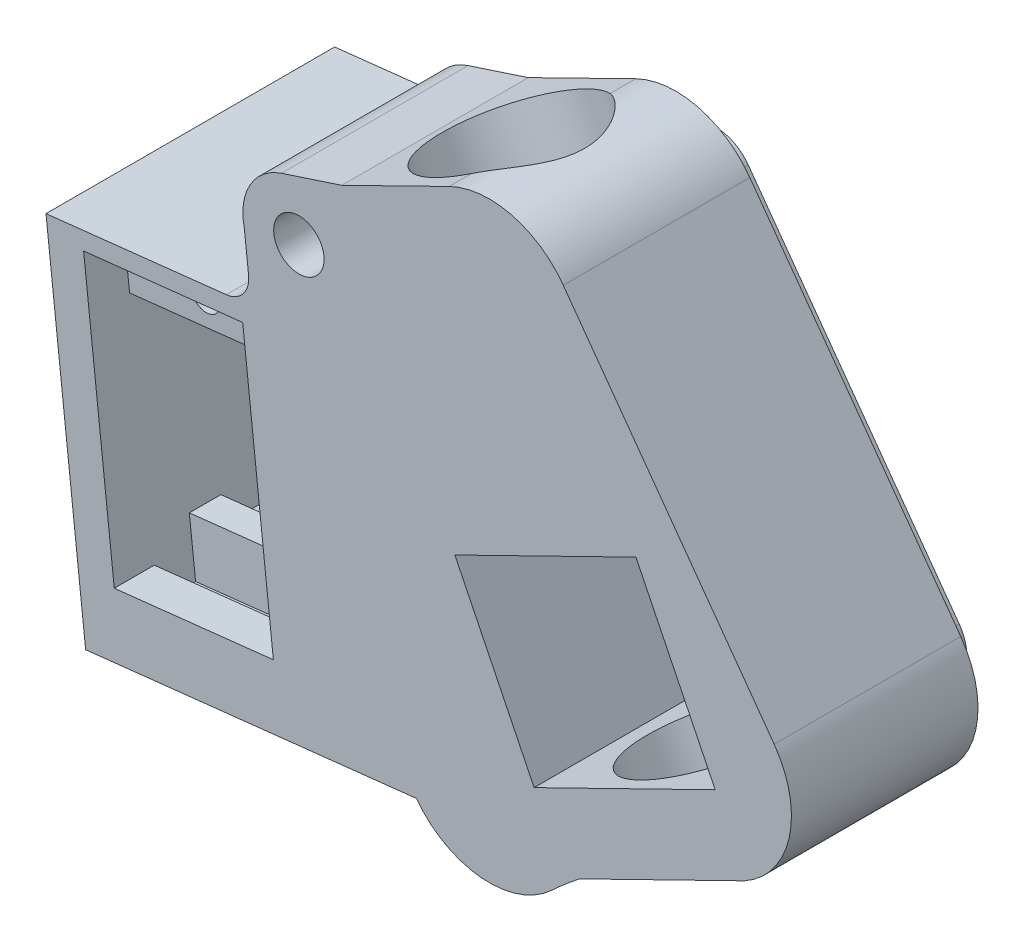
SolidWorks part; units mm, degrees
note: The reader was unsure of these and kept them because the rebuilt part matched: shared geometry of "Sketch1<4>".
ref_plane "Front Plane" through (0, 0, 0) normal (0, 0, 1) x (1, 0, 0)
ref_plane "Top Plane" through (0, 0, 0) normal (0, 1, 0) x (1, 0, 0)
ref_plane "Right Plane" through (0, 0, 0) normal (1, 0, 0) x (0, 0, -1)
sketch "Sketch1" plane through (0, 0, 0) normal (0, 0, 1) x (1, 0, 0)
  line L0 (767.9848, 261.423) -> (751.2472, 284.5967) construction
  line L1 (745.4984, 250.2176) -> (745.4984, 282.7377) construction
  line L2 (767.9848, 261.423) -> (751.2472, 284.5967)
  line L3 (745.4984, 250.2176) -> (745.4984, 282.7377)
  line L5 (771.2793, 263.8025) -> (754.5418, 286.9763)
  line L6 (732.1798, 275.0395) -> (736.9594, 273.4778) construction
  line L7 (736.9594, 285.0516) -> (732.1797, 283.4899) construction
  line L8 (732.1798, 275.0395) -> (736.9594, 273.4778)
  line L9 (736.9594, 285.0516) -> (732.1797, 283.4899)
  line L10 (736.9594, 285.0516) -> (745.4834, 289.236)
  line L11 (739.1483, 270.4598) -> (741.4784, 249.4207)
  line L12 (756.5148, 247.1568) -> (767.2365, 252.4067) construction
  line L13 (741.4344, 250.2176) -> (741.4344, 282.7377) construction
  line L14 (755.8389, 246.8259) -> (768.8985, 253.2205)
  arc A0 (745.4984, 250.2176) -> (750.8405, 247.8971) centre (748.6734, 250.2176) ccw construction
  arc A1 (766.2496, 256.5018) -> (750.8405, 247.8971) centre (775.9784, 220.98) ccw construction
  arc A2 (766.2496, 256.5018) -> (767.9848, 261.423) centre (765.4109, 259.564) ccw construction
  arc A3 (751.2472, 284.5967) -> (745.4984, 282.7377) centre (748.6734, 282.7377) ccw construction
  arc A4 (745.4984, 250.2176) -> (750.8405, 247.8971) centre (748.6734, 250.2176) ccw
  arc A5 (766.2496, 256.5018) -> (750.8405, 247.8971) centre (775.9784, 220.98) ccw
  arc A6 (766.2496, 256.5018) -> (767.9848, 261.423) centre (765.4109, 259.564) ccw
  arc A7 (751.2472, 284.5967) -> (745.4984, 282.7377) centre (748.6734, 282.7377) ccw
  arc A8 (754.5418, 286.9763) -> (745.4834, 289.236) centre (748.6734, 282.7377) ccw
  arc A9 (741.4784, 249.4207) -> (753.6143, 244.927) centre (748.6734, 250.2176) ccw
  arc A10 (755.8389, 246.8259) -> (753.6143, 244.927) centre (775.9784, 220.98) ccw
  arc A11 (768.2831, 252.9192) -> (771.2793, 263.8025) centre (765.4109, 259.564) ccw
  arc A12 (739.1483, 270.4598) -> (736.9594, 273.4778) centre (735.9733, 270.4598) ccw construction
  arc A14 (732.1797, 283.4899) -> (732.1798, 275.0395) centre (733.5603, 279.2647) ccw construction
  arc A15 (739.1483, 270.4598) -> (736.9594, 273.4778) centre (735.9733, 270.4598) ccw
  arc A17 (732.1797, 283.4899) -> (732.1798, 275.0395) centre (733.5603, 279.2647) ccw
  arc A18 (754.5418, 286.9763) -> (741.4344, 282.7377) centre (748.6734, 282.7377) ccw construction
  arc A19 (741.4344, 250.2176) -> (753.6143, 244.927) centre (748.6734, 250.2176) ccw construction
  arc A20 (767.3231, 252.5821) -> (753.6143, 244.927) centre (775.9784, 220.98) ccw construction
  arc A21 (767.3231, 252.5821) -> (771.2793, 263.8025) centre (765.4109, 259.564) ccw construction
  dimension "D1" = 4.064
extrude "Boss-Extrude1" add sketch "Sketch1" along normal blind 15.06 contours L9 A17 L8 A15 L11 A9 A10 A11 L5 A8 L10 A7 L2 A6 A5 A4 L3 | L2 A7 L3 A4 A5 A6
sketch "Sketch4" plane through (0, 0, 15.06) normal (0, 0, 1) x (1, 0, 0)
  line L0 (756.5148, 247.1568) -> (767.2365, 252.4067) construction
  line L1 (746.963, 293.8107) -> (736.2413, 288.5608) construction
  line L2 (756.5148, 247.1568) -> (767.2365, 252.4067)
  line L3 (746.963, 293.8107) -> (736.2413, 288.5608)
  line L4 (746.963, 293.8107) -> (767.2365, 252.4067)
  line L5 (756.5148, 247.1568) -> (736.2413, 288.5608)
extrude "Boss-Extrude2" add sketch "Sketch1<4>" against normal blind 3.175 contours L2 A7 L3 A4 A5 A6
sketch "Sketch1<4>" plane through (0, 0, 0) normal (0, 0, 1) x (1, 0, 0) same geometry as "Sketch1"
sketch "Sketch7" plane through (759.7828, 84.1474, 0) normal (-0.9939, -0.1101, 0) x (0, 0, 1)
  line L0 (15.06, 187.4516) -> (15.06, 166.2838) construction
  line L1 (0, 191.1833) -> (15.06, 191.1833)
  line L2 (0, 191.1833) -> (0, 162.6083)
  line L3 (0, 162.6083) -> (15.06, 162.6083)
  line L4 (15.06, 191.1833) -> (15.06, 162.6083)
  line L6 (0, 187.4516) -> (0, 166.2838) construction
  dimension "D1" = 28.575
extrude "Boss-Extrude3" add sketch "Sketch7" along normal blind 25.4 and the other way blind 2.54
sketch "Sketch8" plane through (0, 0, 15.06) normal (0, 0, 1) x (1, 0, 0)
  line L2 (716.6374, 242.9715) -> (742.8795, 245.8778) construction
  line L3 (723.9356, 257.8352) -> (725.4734, 243.9501) construction
  line L4 (716.6374, 242.9715) -> (713.4919, 271.3728) construction
  line L5 (723.9356, 257.8352) -> (724.616, 251.6912) construction
  circle A0 centre (723.9356, 257.8352) radius 5.1
  dimension "D1" = 10.2
  dimension "D2" = 13.97
  dimension "D3" = 8.89
sketch "Sketch9" plane through (0, 0, 15.06) normal (0, 0, 1) x (1, 0, 0)
  line L1 (716.6374, 242.9715) -> (742.8795, 245.8778) construction
  line L2 (716.6374, 242.9715) -> (713.4919, 271.3728) construction
  line L8 (731.5337, 249.7323) -> (729.1012, 271.696)
  line L9 (729.1012, 271.696) -> (716.4784, 270.298)
  line L10 (716.4784, 270.298) -> (718.9109, 248.3343)
  line L11 (718.9109, 248.3343) -> (731.5337, 249.7323)
  dimension "D1" = 22.098
  dimension "D2" = 5.08
  dimension "D3" = 2.85
  dimension "D4" = 12.7
extrude "Cut-Extrude1" cut sketch "Sketch9" against normal offset from surface (14.552 mm away) 0.254 from offset 0.254 up to face at (743.0241, 266.2605, 0) offset against normal yes
sketch "Sketch11" plane through (0, 0, 0) normal (0, 0, -1) x (-1, 0, 0)
  line L0 (-713.4919, 271.3728) -> (-732.3764, 273.4643)
  line L1 (-713.4919, 271.3728) -> (-735.8301, 273.8468) construction
  line L2 (-732.3764, 273.4643) -> (-735.5219, 245.063)
  line L3 (-716.6374, 242.9715) -> (-742.8795, 245.8778) construction
  line L4 (-735.5219, 245.063) -> (-722.9488, 243.6705)
  line L5 (-739.1484, 220.9799) -> (-739.1483, 270.4598) construction
  line L6 (-739.1484, 220.9799) -> (-739.1483, 270.4598) construction
  line L7 (-735.5219, 245.063) -> (-739.1484, 245.4646)
  line L8 (-739.1484, 245.4646) -> (-739.1483, 270.4598)
  line L10 (-736.9594, 273.4778) -> (-735.8301, 273.8468)
  line L16 (-732.1797, 283.4899) -> (-736.9594, 285.0516)
  line L17 (-736.9594, 285.0516) -> (-745.4834, 289.236)
  line L18 (-754.5418, 286.9763) -> (-771.2793, 263.8025)
  line L19 (-768.8985, 253.2205) -> (-755.8389, 246.8259)
  line L21 (-742.8795, 245.8778) -> (-716.6374, 242.9715)
  line L22 (-716.6374, 242.9715) -> (-713.4919, 271.3728)
  line L23 (-713.4919, 271.3728) -> (-735.8301, 273.8468)
  line L25 (-735.8301, 273.8468) -> (-732.1798, 275.0395)
  line L26 (-732.1797, 283.4899) -> (-736.9594, 285.0516)
  line L27 (-736.9594, 285.0516) -> (-745.4834, 289.236)
  line L28 (-754.5418, 286.9763) -> (-771.2793, 263.8025)
  line L29 (-768.8985, 253.2205) -> (-755.8389, 246.8259)
  line L31 (-742.8795, 245.8778) -> (-722.9488, 243.6705)
  line L33 (-713.4919, 271.3728) -> (-735.8301, 273.8468)
  line L35 (-735.8301, 273.8468) -> (-732.1798, 275.0395)
  arc A0 (-736.9594, 273.4778) -> (-739.1483, 270.4598) centre (-735.9733, 270.4598) ccw construction
  arc A1 (-736.9594, 273.4778) -> (-739.1483, 270.4598) centre (-735.9733, 270.4598) ccw
  arc A6 (-745.4834, 289.236) -> (-754.5418, 286.9763) centre (-748.6734, 282.7377) ccw
  arc A7 (-771.2793, 263.8025) -> (-768.8985, 253.2205) centre (-765.4109, 259.564) ccw
  arc A8 (-753.6143, 244.927) -> (-755.8389, 246.8259) centre (-775.9784, 220.98) ccw
  arc A9 (-753.6143, 244.927) -> (-742.8795, 245.8778) centre (-748.6734, 250.2176) ccw
  arc A11 (-732.1798, 275.0395) -> (-732.1797, 283.4899) centre (-733.5603, 279.2647) ccw
  arc A12 (-745.4834, 289.236) -> (-754.5418, 286.9763) centre (-748.6734, 282.7377) ccw
  arc A13 (-771.2793, 263.8025) -> (-768.8985, 253.2205) centre (-765.4109, 259.564) ccw
  arc A14 (-753.6143, 244.927) -> (-755.8389, 246.8259) centre (-775.9784, 220.98) ccw
  arc A15 (-753.6143, 244.927) -> (-742.8795, 245.8778) centre (-748.6734, 250.2176) ccw
  arc A17 (-732.1798, 275.0395) -> (-732.1797, 283.4899) centre (-733.5603, 279.2647) ccw
  dimension "D1" = 19
  dimension "D2" = 0
extrude "Boss-Extrude4" add sketch "Sketch11" along normal blind 8.1
extrude "Cut-Extrude3" cut sketch "Sketch8" against normal through all
sketch "Sketch15" plane through (48.6865, -99.4313, 0) normal (0.4398, -0.8981, 0) x (0.8981, 0.4398, 0)
  line L0 (787.3745, 15.06) -> (801.9156, 15.06) construction
  line L1 (801.9156, 15.06) -> (801.9156, 0) construction
  circle A0 centre (794.096, 7.5321) radius 5.969 construction
  circle A1 centre (794.096, 7.5321) radius 6.096
  dimension "D1" = 11.938
  dimension "D2" = 7.5279
  dimension "D3" = 7.8196
  dimension "D4" = 0.127
extrude "Cut-Extrude4" cut sketch "Sketch15" against normal through all
sketch "Sketch20" plane through (0, 0, 15.06) normal (0, 0, 1) x (1, 0, 0)
  line L0 (718.9109, 248.3343) -> (731.5337, 249.7323) construction
  line L1 (716.4784, 270.298) -> (718.9109, 248.3343) construction
  line L2 (729.1012, 271.696) -> (716.4784, 270.298) construction
  line L3 (731.5337, 249.7323) -> (729.1012, 271.696) construction
  line L4 (718.9109, 248.3343) -> (731.5337, 249.7323)
  line L5 (732.1798, 275.0395) -> (735.8301, 273.8468)
  line L6 (735.8301, 273.8468) -> (713.4919, 271.3728)
  line L7 (713.4919, 271.3728) -> (716.6374, 242.9715)
  line L8 (716.6374, 242.9715) -> (742.8795, 245.8778)
  line L9 (755.8389, 246.8259) -> (768.8985, 253.2205)
  line L10 (732.1798, 275.0395) -> (735.8301, 273.8468)
  line L11 (735.8301, 273.8468) -> (713.4919, 271.3728)
  line L12 (713.4919, 271.3728) -> (716.6374, 242.9715)
  line L13 (716.6374, 242.9715) -> (742.8795, 245.8778)
  line L15 (716.4784, 270.298) -> (718.9109, 248.3343)
  line L16 (729.1012, 271.696) -> (716.4784, 270.298)
  line L17 (731.5337, 249.7323) -> (729.1012, 271.696)
  line L26 (755.8389, 246.8259) -> (768.8985, 253.2205)
  line L27 (771.2793, 263.8025) -> (754.5418, 286.9763)
  line L29 (745.4834, 289.236) -> (736.9594, 285.0516)
  line L30 (745.4834, 289.236) -> (736.9594, 285.0516)
  line L31 (736.9594, 285.0516) -> (732.1797, 283.4899)
  line L32 (736.9594, 285.0516) -> (732.1797, 283.4899)
  line L36 (771.2793, 263.8025) -> (754.5418, 286.9763)
  arc A2 (742.8795, 245.8778) -> (753.6143, 244.927) centre (748.6734, 250.2176) ccw
  arc A3 (755.8389, 246.8259) -> (753.6143, 244.927) centre (775.9784, 220.98) ccw
  arc A4 (742.8795, 245.8778) -> (753.6143, 244.927) centre (748.6734, 250.2176) ccw
  arc A9 (755.8389, 246.8259) -> (753.6143, 244.927) centre (775.9784, 220.98) ccw
  arc A10 (768.8985, 253.2205) -> (771.2793, 263.8025) centre (765.4109, 259.564) ccw
  arc A14 (732.1797, 283.4899) -> (732.1798, 275.0395) centre (733.5603, 279.2647) ccw
  arc A15 (732.1797, 283.4899) -> (732.1798, 275.0395) centre (733.5603, 279.2647) ccw
  arc A16 (768.8985, 253.2205) -> (771.2793, 263.8025) centre (765.4109, 259.564) ccw
  arc A18 (754.5418, 286.9763) -> (745.4834, 289.236) centre (748.6734, 282.7377) ccw
  arc A19 (754.5418, 286.9763) -> (745.4834, 289.236) centre (748.6734, 282.7377) ccw
  dimension "D1" = 0
extrude "Cut-Extrude6" cut sketch "Sketch20" against normal up to surface (0.254 mm away) up to face at (729.0356, 257.8352, 14.806)
sketch "Sketch22" plane through (-18.4589, 166.6692, 0) normal (-0.1101, 0.9939, 0) x (0.9939, 0.1101, 0)
  line L0 (741.8783, -0.254) -> (741.8783, -14.806) construction
  line L1 (741.8783, -8.631) -> (754.5783, -8.631)
  line L2 (741.8783, -8.631) -> (741.8783, -11.631)
  line L3 (741.8783, -11.631) -> (754.5783, -11.631)
  line L4 (754.5783, -8.631) -> (754.5783, -11.631)
  line L5 (754.5783, -0.254) -> (754.5783, -14.806) construction
  line L6 (741.8783, -14.806) -> (754.5783, -14.806) construction
  dimension "D1" = 3.175
  dimension "D2" = 3
extrude "Cut-Extrude8" cut sketch "Sketch22" against normal blind 2.5
sketch "Sketch23" plane through (0, 0, 14.806) normal (0, 0, 1) x (1, 0, 0)
  line L0 (716.4784, 270.298) -> (718.9109, 248.3343) construction
  line L1 (716.9473, 266.0639) -> (729.5701, 267.4619)
  line L9 (731.5337, 249.7323) -> (729.1012, 271.696) construction
  line L10 (729.1012, 271.696) -> (716.4784, 270.298) construction
  line L11 (716.9473, 266.0639) -> (716.4784, 270.298)
  line L12 (716.4784, 270.298) -> (729.1012, 271.696)
  line L13 (729.1012, 271.696) -> (729.5701, 267.4619)
  circle A0 centre (723.0242, 268.88) radius 1.13
  circle A4 centre (723.0242, 268.88) radius 2.13 construction
  dimension "D1" = 1
  dimension "D2" = 2.26
  dimension "D3" = 6.35
extrude "Boss-Extrude5" add sketch "Sketch23" against normal up to surface (11.377 mm away) from offset 3.175 offset against normal yes
sketch "Sketch24" plane through (0, 0, 0.254) normal (0, 0, 1) x (1, 0, 0)
  line L0 (716.9473, 266.0639) -> (717.2775, 263.0822)
  line L1 (718.9109, 248.3343) -> (716.9473, 266.0639) construction
  line L7 (717.2775, 263.0822) -> (729.9004, 264.4802)
  line L8 (729.9004, 264.4802) -> (729.5701, 267.4619)
  line L9 (716.9473, 266.0639) -> (729.5701, 267.4619)
  line L10 (729.5701, 267.4619) -> (731.5337, 249.7323) construction
  dimension "D1" = 3
  dimension "D2" = 0
extrude "Cut-Extrude9" cut sketch "Sketch24" against normal blind 2
sketch "Sketch25" plane through (-18.4589, 166.6692, 0) normal (-0.1101, 0.9939, 0) x (0.9939, 0.1101, 0)
  line L0 (754.5783, -0.254) -> (754.5783, -8.631) construction
  line L1 (741.8783, -8.631) -> (754.5783, -8.631)
  line L2 (741.8783, -8.631) -> (741.8783, -6.131)
  line L3 (741.8783, -6.131) -> (754.5783, -6.131)
  line L4 (754.5783, -8.631) -> (754.5783, -6.131)
  dimension "D1" = 2.5
extrude "Boss-Extrude6" add sketch "Sketch25" along normal blind 2
sketch "Sketch27" plane through (0, 0, -8.1) normal (0, 0, -1) x (-1, 0, 0)
  circle A0 centre (-727.7102, 252.3693) radius 1.5049 construction
  circle A1 centre (-721.4484, 251.6758) radius 1.5049 construction
  circle A2 centre (-727.7102, 252.3693) radius 1.5049
  circle A3 centre (-721.4484, 251.6758) radius 1.5049
ref_plane "Plane1" through (739.1483, 270.4598, 0) normal (0, -1, 0) x (-1, 0, 0)
sketch "Sketch29" plane through (0, 0, 14.806) normal (0, 0, 1) x (1, 0, 0)
  line L1 (756.4007, 247.101) -> (767.3505, 252.4625) construction
  line L3 (756.4007, 247.101) -> (767.3505, 252.4625) construction
  line L4 (752.228, 251.2931) -> (766.5979, 258.3293)
  line L5 (752.228, 251.2931) -> (745.9394, 264.1361)
  line L6 (766.5979, 258.3293) -> (760.3093, 271.1723)
  line L7 (745.9394, 264.1361) -> (760.3093, 271.1723)
  line L8 (761.8756, 249.7817) -> (755.62, 262.5574) construction
  point P0 (761.8756, 249.7817)
  point P7 (753.1244, 267.6542)
  dimension "D1" = 16
  dimension "D2" = 14.3
  dimension "D3" = 5.6
extrude "Cut-Extrude11" cut sketch "Sketch29" against normal through all
sketch "Sketch30" plane through (0, 0, 14.806) normal (0, 0, 1) x (1, 0, 0)
  line L0 (713.4919, 271.3728) -> (735.8301, 273.8468) construction
  line L1 (735.8301, 273.8468) -> (732.1798, 275.0395) construction
  line L2 (729.7894, 273.1778) -> (735.8301, 273.8468)
  line L3 (735.8301, 273.8468) -> (732.1798, 275.0395)
  line L4 (729.223, 278.2921) -> (729.7894, 273.1778)
  arc A0 (732.1797, 283.4899) -> (732.1798, 275.0395) centre (733.5603, 279.2647) ccw construction
  arc A1 (729.223, 278.2921) -> (732.1798, 275.0395) centre (733.5603, 279.2647) ccw
extrude "Boss-Extrude7" add sketch "Sketch30" against normal up to surface (19.886 mm away)
fillet "Fillet1" radius 2 1 edges at (729.7894, 273.1778, 4.863)
sketch "Sketch31" plane through (0, 0, 0) normal (0, 0, -1) x (-1, 0, 0)
  circle A0 centre (-733.5603, 279.2647) radius 2 construction
  circle A1 centre (-733.5603, 279.2647) radius 2
extrude "Cut-Extrude12" cut sketch "Sketch31" against normal through all
